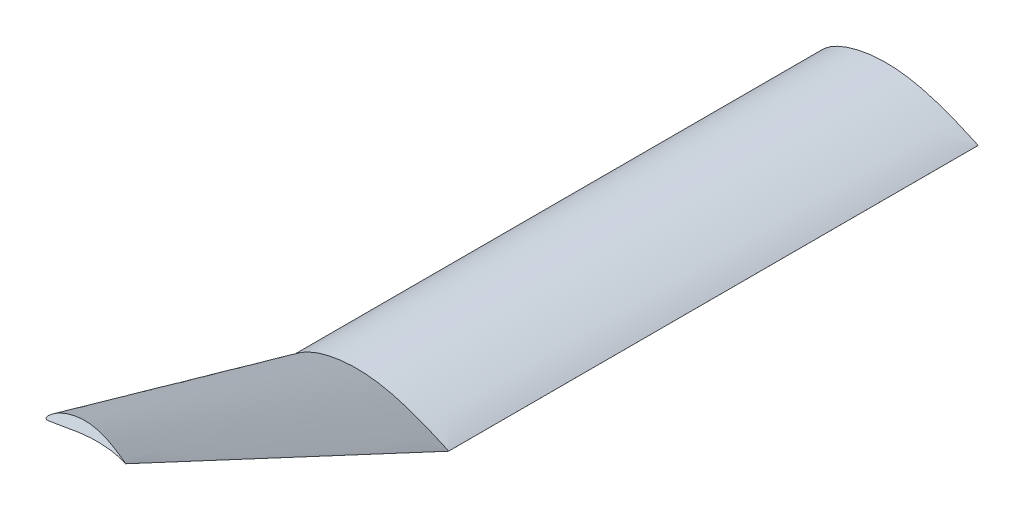
SolidWorks part; units mm, degrees
ref_plane "Front Plane" through (0, 0, 0) normal (0, 0, 1) x (1, 0, 0)
ref_plane "Top Plane" through (0, 0, 0) normal (0, 1, 0) x (1, 0, 0)
ref_plane "Right Plane" through (0, 0, 0) normal (1, 0, 0) x (0, 0, -1)
curve "Curve1"
curve "Curve6"
curve "Curve7"
curve "Curve8"
sketch "Sketch3" plane through (0, 0, 0) normal (0, 0, 1) x (1, 0, 0)
  line L0 (0, 0) -> (50, 0) construction
  line L1 (0.2298, 0.0405) -> (0.2298, 0.0158) construction
  line L2 (0.1804, 0.0405) -> (0.2298, 0.0405)
  line L3 (0.1804, 0.0405) -> (0.1804, -0.0089)
  line L4 (0.1804, -0.0089) -> (0.2298, -0.0089)
  line L5 (0.2298, 0.0405) -> (0.2298, -0.0089)
  line L6 (0.4642, 0.0242) -> (0.4889, 0.0242)
  line L7 (0.4642, 0.0242) -> (0.4642, -0.0005)
  line L8 (0.4642, -0.0005) -> (0.4889, -0.0005)
  line L9 (0.4889, 0.0242) -> (0.4889, -0.0005)
  line L10 (0.2298, 0.0158) -> (0.2146, 0.0158) construction
  line L11 (0.2146, 0.0158) -> (0.2146, 0.0405) construction
  line L12 (0.2146, 0.0405) -> (0.2298, 0.0405) construction
  line L13 (0, 0) -> (500, 0) construction
  line L14 (0.1804, 0.0458) -> (0.1804, -0.0178) construction
  line L15 (0, 0) -> (0, -165.9812) construction
  line L16 (0, -165.9812) -> (300, -165.9812) construction
  line L17 (72.7802, 36.2202) -> (92.7802, 36.2202) construction
  line L18 (70.2802, 13.7202) -> (95.2802, 13.7202)
  line L19 (70.2802, 13.7202) -> (70.2802, 38.7202)
  line L20 (70.2802, 38.7202) -> (95.2802, 38.7202)
  line L21 (95.2802, 13.7202) -> (95.2802, 38.7202)
  line L22 (92.7802, 16.2202) -> (92.7802, 36.2202) construction
  line L23 (72.7802, 16.2202) -> (92.7802, 16.2202) construction
  line L24 (72.7802, 16.2202) -> (72.7802, 36.2202) construction
  line L25 (300, -0.018) -> (300, 0.015)
  line L26 (172.9506, 31.8748) -> (182.9506, 31.8748)
  line L27 (172.9506, 31.8748) -> (172.9506, 21.8748)
  line L28 (172.9506, 21.8748) -> (182.9506, 21.8748)
  line L29 (182.9506, 31.8748) -> (182.9506, 21.8748)
  spline S0 degree 3 poles (1.0002, -0.0023) (1, 0) (1.0002, 0.0023) (0.9919, 0.0001) (0.9849, 0.0027) (0.9729, 0.003) (0.9609, 0.0043) (0.9483, 0.0054) (0.9357, 0.0065) (0.9231, 0.0077) (0.9104, 0.0088) (0.8978, 0.01) (0.8852, 0.0111) (0.8725, 0.0123) (0.8599, 0.0134) (0.8473, 0.0146) (0.8347, 0.0157) (0.8221, 0.0168) (0.8094, 0.0179) (0.7968, 0.019) (0.7842, 0.0201) (0.7716, 0.0211) (0.759, 0.0222) (0.7464, 0.0232) (0.7337, 0.0243) (0.7211, 0.0253) (0.7085, 0.0263) (0.6959, 0.0273) (0.6833, 0.0283) (0.6706, 0.0293) (0.658, 0.0303) (0.6454, 0.0313) (0.6328, 0.0322) (0.6202, 0.0331) (0.6076, 0.0341) (0.595, 0.035) (0.5823, 0.0358) (0.5697, 0.0367) (0.5571, 0.0375) (0.5446, 0.0384) (0.532, 0.0392) (0.5194, 0.0399) (0.5068, 0.0407) (0.4942, 0.0414) (0.4816, 0.0421) (0.469, 0.0427) (0.4565, 0.0434) (0.4439, 0.044) (0.4313, 0.0445) (0.4188, 0.0451) (0.4062, 0.0456) (0.3936, 0.046) (0.3811, 0.0464) (0.3685, 0.0468) (0.356, 0.0472) (0.3435, 0.0475) (0.3309, 0.0477) (0.3184, 0.0479) (0.3059, 0.0481) (0.2934, 0.0482) (0.2809, 0.0482) (0.2685, 0.0482) (0.256, 0.0481) (0.2436, 0.0479) (0.2312, 0.0477) (0.2189, 0.0474) (0.2065, 0.047) (0.1942, 0.0465) (0.182, 0.0459) (0.1698, 0.0452) (0.1576, 0.0444) (0.1456, 0.0434) (0.1336, 0.0423) (0.1217, 0.0411) (0.1099, 0.0397) (0.0983, 0.038) (0.0868, 0.0362) (0.0756, 0.0342) (0.0647, 0.0319) (0.0541, 0.0294) (0.0441, 0.0266) (0.0348, 0.0236) (0.0266, 0.0205) (0.0197, 0.0175) (0.0142, 0.0146) (0.0101, 0.012) (0.007, 0.0098) (0.0047, 0.0078) (0.003, 0.006) (0.0018, 0.0045) (0.0009, 0.003) (0.0003, 0.0017) (0, 0.0004) (0, -0.0008) (0.0005, -0.0021) (0.0015, -0.0032) (0.0028, -0.0043) (0.0046, -0.0054) (0.0068, -0.0066) (0.0097, -0.0078) (0.0135, -0.0091) (0.0186, -0.0106) (0.0252, -0.0121) (0.0334, -0.0135) (0.043, -0.0148) (0.0536, -0.0159) (0.0648, -0.0167) (0.0764, -0.0173) (0.0882, -0.0177) (0.1003, -0.018) (0.1125, -0.0182) (0.1247, -0.0183) (0.1371, -0.0183) (0.1495, -0.0182) (0.162, -0.0181) (0.1745, -0.0179) (0.187, -0.0176) (0.1996, -0.0174) (0.2122, -0.0171) (0.2248, -0.0167) (0.2375, -0.0164) (0.2501, -0.016) (0.2628, -0.0156) (0.2755, -0.0152) (0.2882, -0.0147) (0.3009, -0.0143) (0.3136, -0.0139) (0.3263, -0.0134) (0.339, -0.0129) (0.3517, -0.0125) (0.3644, -0.012) (0.3771, -0.0116) (0.3897, -0.0111) (0.4024, -0.0106) (0.4151, -0.0102) (0.4277, -0.0098) (0.4404, -0.0093) (0.4531, -0.0089) (0.4657, -0.0085) (0.4784, -0.0081) (0.4911, -0.0077) (0.5037, -0.0073) (0.5164, -0.0069) (0.5291, -0.0066) (0.5417, -0.0062) (0.5544, -0.0059) (0.5671, -0.0055) (0.5798, -0.0052) (0.5924, -0.0049) (0.6051, -0.0046) (0.6178, -0.0044) (0.6304, -0.0041) (0.6431, -0.0039) (0.6558, -0.0036) (0.6685, -0.0034) (0.6811, -0.0032) (0.6938, -0.003) (0.7065, -0.0029) (0.7192, -0.0027) (0.7318, -0.0026) (0.7445, -0.0024) (0.7572, -0.0023) (0.7699, -0.0022) (0.7826, -0.0021) (0.7953, -0.002) (0.8079, -0.0019) (0.8206, -0.0019) (0.8333, -0.0018) (0.846, -0.0017) (0.8588, -0.0017) (0.8715, -0.0016) (0.8842, -0.0015) (0.8969, -0.0015) (0.9096, -0.0014) (0.9223, -0.0013) (0.935, -0.0012) (0.9477, -0.0011) (0.9604, -0.0011) (0.9725, -0.0007) (0.9848, -0.0014) (0.9918, 0.0007) (1.0002, -0.0023) (1, 0) (1.0002, 0.0023) knots -0.007874 -0.002894 -0.000332 0 0.000332 0.002885 0.007815 0.013623 0.01978 0.026037 0.032316 0.038604 0.044895 0.051184 0.057469 0.06375 0.070028 0.076304 0.082578 0.088851 0.095124 0.101396 0.107668 0.113941 0.120213 0.126487 0.132762 0.139036 0.145311 0.151585 0.157859 0.16413 0.170401 0.17667 0.182937 0.189202 0.195466 0.201728 0.207987 0.214245 0.2205 0.226754 0.233005 0.239253 0.2455 0.251744 0.257986 0.264226 0.270464 0.2767 0.282933 0.289165 0.295394 0.30162 0.307843 0.314063 0.32028 0.326491 0.332699 0.3389 0.345096 0.351285 0.357467 0.363641 0.369805 0.375959 0.382101 0.38823 0.394345 0.400443 0.406521 0.412577 0.418607 0.424607 0.430573 0.436498 0.442374 0.448192 0.453938 0.459595 0.465142 0.470542 0.475738 0.480625 0.48504 0.488808 0.491844 0.494208 0.496047 0.497501 0.498679 0.499657 0.500486 0.501199 0.501823 0.502412 0.503041 0.50376 0.504602 0.505602 0.50682 0.508337 0.510284 0.512841 0.516185 0.520365 0.525232 0.530552 0.536146 0.541914 0.547804 0.553781 0.559821 0.565909 0.57203 0.578179 0.584352 0.590546 0.596759 0.60299 0.609237 0.615497 0.621768 0.62805 0.634339 0.640634 0.646932 0.653231 0.659529 0.665824 0.672115 0.678404 0.684692 0.690977 0.69726 0.703542 0.709822 0.716099 0.722375 0.728651 0.734927 0.741206 0.747487 0.753768 0.76005 0.766331 0.772611 0.778892 0.785172 0.791451 0.79773 0.804009 0.810289 0.816569 0.822848 0.829126 0.835406 0.841685 0.847965 0.854245 0.860527 0.866808 0.87309 0.879373 0.885657 0.891942 0.898228 0.904515 0.910804 0.917095 0.923389 0.929686 0.935986 0.942288 0.948588 0.954885 0.961183 0.96748 0.973774 0.980051 0.986247 0.992126 0.997106 0.999668 1 1.000332 1.002885 1.007815 only from (1, 0) to (1, 0) construction
  spline S1 degree 3 poles (1.0002, -0.0023) (1, 0) (1.0002, 0.0023) (0.9919, 0.0001) (0.9849, 0.0027) (0.9729, 0.003) (0.9609, 0.0043) (0.9483, 0.0054) (0.9357, 0.0065) (0.9231, 0.0077) (0.9104, 0.0088) (0.8978, 0.01) (0.8852, 0.0111) (0.8725, 0.0123) (0.8599, 0.0134) (0.8473, 0.0146) (0.8347, 0.0157) (0.8221, 0.0168) (0.8094, 0.0179) (0.7968, 0.019) (0.7842, 0.0201) (0.7716, 0.0211) (0.759, 0.0222) (0.7464, 0.0232) (0.7337, 0.0243) (0.7211, 0.0253) (0.7085, 0.0263) (0.6959, 0.0273) (0.6833, 0.0283) (0.6706, 0.0293) (0.658, 0.0303) (0.6454, 0.0313) (0.6328, 0.0322) (0.6202, 0.0331) (0.6076, 0.0341) (0.595, 0.035) (0.5823, 0.0358) (0.5697, 0.0367) (0.5571, 0.0375) (0.5446, 0.0384) (0.532, 0.0392) (0.5194, 0.0399) (0.5068, 0.0407) (0.4942, 0.0414) (0.4816, 0.0421) (0.469, 0.0427) (0.4565, 0.0434) (0.4439, 0.044) (0.4313, 0.0445) (0.4188, 0.0451) (0.4062, 0.0456) (0.3936, 0.046) (0.3811, 0.0464) (0.3685, 0.0468) (0.356, 0.0472) (0.3435, 0.0475) (0.3309, 0.0477) (0.3184, 0.0479) (0.3059, 0.0481) (0.2934, 0.0482) (0.2809, 0.0482) (0.2685, 0.0482) (0.256, 0.0481) (0.2436, 0.0479) (0.2312, 0.0477) (0.2189, 0.0474) (0.2065, 0.047) (0.1942, 0.0465) (0.182, 0.0459) (0.1698, 0.0452) (0.1576, 0.0444) (0.1456, 0.0434) (0.1336, 0.0423) (0.1217, 0.0411) (0.1099, 0.0397) (0.0983, 0.038) (0.0868, 0.0362) (0.0756, 0.0342) (0.0647, 0.0319) (0.0541, 0.0294) (0.0441, 0.0266) (0.0348, 0.0236) (0.0266, 0.0205) (0.0197, 0.0175) (0.0142, 0.0146) (0.0101, 0.012) (0.007, 0.0098) (0.0047, 0.0078) (0.003, 0.006) (0.0018, 0.0045) (0.0009, 0.003) (0.0003, 0.0017) (0, 0.0004) (0, -0.0008) (0.0005, -0.0021) (0.0015, -0.0032) (0.0028, -0.0043) (0.0046, -0.0054) (0.0068, -0.0066) (0.0097, -0.0078) (0.0135, -0.0091) (0.0186, -0.0106) (0.0252, -0.0121) (0.0334, -0.0135) (0.043, -0.0148) (0.0536, -0.0159) (0.0648, -0.0167) (0.0764, -0.0173) (0.0882, -0.0177) (0.1003, -0.018) (0.1125, -0.0182) (0.1247, -0.0183) (0.1371, -0.0183) (0.1495, -0.0182) (0.162, -0.0181) (0.1745, -0.0179) (0.187, -0.0176) (0.1996, -0.0174) (0.2122, -0.0171) (0.2248, -0.0167) (0.2375, -0.0164) (0.2501, -0.016) (0.2628, -0.0156) (0.2755, -0.0152) (0.2882, -0.0147) (0.3009, -0.0143) (0.3136, -0.0139) (0.3263, -0.0134) (0.339, -0.0129) (0.3517, -0.0125) (0.3644, -0.012) (0.3771, -0.0116) (0.3897, -0.0111) (0.4024, -0.0106) (0.4151, -0.0102) (0.4277, -0.0098) (0.4404, -0.0093) (0.4531, -0.0089) (0.4657, -0.0085) (0.4784, -0.0081) (0.4911, -0.0077) (0.5037, -0.0073) (0.5164, -0.0069) (0.5291, -0.0066) (0.5417, -0.0062) (0.5544, -0.0059) (0.5671, -0.0055) (0.5798, -0.0052) (0.5924, -0.0049) (0.6051, -0.0046) (0.6178, -0.0044) (0.6304, -0.0041) (0.6431, -0.0039) (0.6558, -0.0036) (0.6685, -0.0034) (0.6811, -0.0032) (0.6938, -0.003) (0.7065, -0.0029) (0.7192, -0.0027) (0.7318, -0.0026) (0.7445, -0.0024) (0.7572, -0.0023) (0.7699, -0.0022) (0.7826, -0.0021) (0.7953, -0.002) (0.8079, -0.0019) (0.8206, -0.0019) (0.8333, -0.0018) (0.846, -0.0017) (0.8588, -0.0017) (0.8715, -0.0016) (0.8842, -0.0015) (0.8969, -0.0015) (0.9096, -0.0014) (0.9223, -0.0013) (0.935, -0.0012) (0.9477, -0.0011) (0.9604, -0.0011) (0.9725, -0.0007) (0.9848, -0.0014) (0.9918, 0.0007) (1.0002, -0.0023) (1, 0) (1.0002, 0.0023) knots -0.007874 -0.002894 -0.000332 0 0.000332 0.002885 0.007815 0.013623 0.01978 0.026037 0.032316 0.038604 0.044895 0.051184 0.057469 0.06375 0.070028 0.076304 0.082578 0.088851 0.095124 0.101396 0.107668 0.113941 0.120213 0.126487 0.132762 0.139036 0.145311 0.151585 0.157859 0.16413 0.170401 0.17667 0.182937 0.189202 0.195466 0.201728 0.207987 0.214245 0.2205 0.226754 0.233005 0.239253 0.2455 0.251744 0.257986 0.264226 0.270464 0.2767 0.282933 0.289165 0.295394 0.30162 0.307843 0.314063 0.32028 0.326491 0.332699 0.3389 0.345096 0.351285 0.357467 0.363641 0.369805 0.375959 0.382101 0.38823 0.394345 0.400443 0.406521 0.412577 0.418607 0.424607 0.430573 0.436498 0.442374 0.448192 0.453938 0.459595 0.465142 0.470542 0.475738 0.480625 0.48504 0.488808 0.491844 0.494208 0.496047 0.497501 0.498679 0.499657 0.500486 0.501199 0.501823 0.502412 0.503041 0.50376 0.504602 0.505602 0.50682 0.508337 0.510284 0.512841 0.516185 0.520365 0.525232 0.530552 0.536146 0.541914 0.547804 0.553781 0.559821 0.565909 0.57203 0.578179 0.584352 0.590546 0.596759 0.60299 0.609237 0.615497 0.621768 0.62805 0.634339 0.640634 0.646932 0.653231 0.659529 0.665824 0.672115 0.678404 0.684692 0.690977 0.69726 0.703542 0.709822 0.716099 0.722375 0.728651 0.734927 0.741206 0.747487 0.753768 0.76005 0.766331 0.772611 0.778892 0.785172 0.791451 0.79773 0.804009 0.810289 0.816569 0.822848 0.829126 0.835406 0.841685 0.847965 0.854245 0.860527 0.866808 0.87309 0.879373 0.885657 0.891942 0.898228 0.904515 0.910804 0.917095 0.923389 0.929686 0.935986 0.942288 0.948588 0.954885 0.961183 0.96748 0.973774 0.980051 0.986247 0.992126 0.997106 0.999668 1 1.000332 1.002885 1.007815 only from (1, 0) to (1, 0) construction
  spline S2 degree 3 poles (500.0959, -1.1537) (499.9892, 0.0005) (500.0921, 1.1423) (495.9334, 0.0411) (492.471, 1.3334) (486.441, 1.5239) (480.4457, 2.1624) (474.1516, 2.6955) (467.853, 3.2724) (461.5326, 3.8433) (455.2123, 4.419) (448.8921, 4.9943) (442.5755, 5.5699) (436.262, 6.142) (429.9511, 6.7101) (423.6424, 7.2769) (417.3349, 7.8378) (411.0282, 8.3936) (404.7219, 8.9456) (398.4154, 9.4908) (392.1084, 10.0313) (385.8007, 10.567) (379.4922, 11.0968) (373.1826, 11.6221) (366.8717, 12.1412) (360.56, 12.6562) (354.2482, 13.167) (347.9364, 13.6717) (341.6252, 14.172) (335.3149, 14.6658) (329.0056, 15.1544) (322.6972, 15.6341) (316.3902, 16.1098) (310.0841, 16.5743) (303.7793, 17.0336) (297.4758, 17.4828) (291.1738, 17.9236) (284.8734, 18.3542) (278.5742, 18.7741) (272.2766, 19.1842) (265.9803, 19.5806) (259.6857, 19.9669) (253.3925, 20.3385) (247.1009, 20.6976) (240.8108, 21.0438) (234.5219, 21.3728) (228.2344, 21.6877) (221.9482, 21.986) (215.6634, 22.269) (209.38, 22.5336) (203.0985, 22.7823) (196.8192, 23.011) (190.5422, 23.2214) (184.2678, 23.4112) (177.9968, 23.5814) (171.7294, 23.7279) (165.4666, 23.8538) (159.2085, 23.9536) (152.9563, 24.0285) (146.7104, 24.0763) (140.4718, 24.0951) (134.2418, 24.0833) (128.0212, 24.0398) (121.8114, 23.9589) (115.6139, 23.8431) (109.4305, 23.6857) (103.2636, 23.4864) (97.1155, 23.2386) (90.9895, 22.9417) (84.8889, 22.5902) (78.8182, 22.1795) (72.7826, 21.7035) (66.7884, 21.1583) (60.844, 20.5334) (54.9591, 19.8268) (49.1468, 19.0246) (43.424, 18.1218) (37.8124, 17.1067) (32.343, 15.9694) (27.0604, 14.7062) (22.0393, 13.3164) (17.395, 11.8221) (13.2795, 10.2688) (9.8299, 8.731) (7.0994, 7.2913) (5.0301, 6.0034) (3.4945, 4.8762) (2.3559, 3.8907) (1.5099, 3.0166) (0.8848, 2.2285) (0.4335, 1.5087) (0.1314, 0.8425) (-0.0182, 0.2062) (0.0104, -0.4232) (0.2632, -1.0376) (0.7397, -1.6094) (1.4111, -2.154) (2.2826, -2.7045) (3.4007, -3.2811) (4.8511, -3.898) (6.7651, -4.5654) (9.3055, -5.2886) (12.6143, -6.039) (16.7206, -6.7632) (21.5126, -7.4019) (26.7966, -7.9252) (32.394, -8.3361) (38.1897, -8.6462) (44.118, -8.8675) (50.1404, -9.0195) (56.2306, -9.1096) (62.3698, -9.1496) (68.5456, -9.1443) (74.75, -9.104) (80.9785, -9.0332) (87.2282, -8.9364) (93.4969, -8.818) (99.783, -8.6804) (106.0845, -8.5272) (112.3995, -8.3597) (118.7258, -8.1811) (125.0618, -7.9892) (131.4053, -7.7924) (137.7541, -7.5838) (144.1059, -7.37) (150.4584, -7.1501) (156.8097, -6.9267) (163.1584, -6.6992) (169.5042, -6.4709) (175.8475, -6.2404) (182.1887, -6.0105) (188.5278, -5.7806) (194.865, -5.5531) (201.2002, -5.325) (207.5338, -5.1031) (213.8656, -4.8806) (220.1961, -4.6635) (226.5264, -4.4495) (232.8578, -4.2412) (239.1911, -4.0373) (245.5262, -3.8375) (251.8626, -3.6436) (258.1993, -3.458) (264.5356, -3.2755) (270.8718, -3.1019) (277.2076, -2.9318) (283.5434, -2.7691) (289.8787, -2.6119) (296.2141, -2.4645) (302.5496, -2.3201) (308.8856, -2.184) (315.2216, -2.0569) (321.5574, -1.9335) (327.8933, -1.8191) (334.2294, -1.7131) (340.5661, -1.6125) (346.9033, -1.5208) (353.2413, -1.4364) (359.58, -1.3587) (365.9191, -1.2888) (372.2588, -1.223) (378.5993, -1.1661) (384.9408, -1.1114) (391.2835, -1.0632) (397.6273, -1.0167) (403.9727, -0.9749) (410.3197, -0.9366) (416.669, -0.8947) (423.021, -0.8606) (429.376, -0.8257) (435.7337, -0.7924) (442.0922, -0.7597) (448.4498, -0.726) (454.8061, -0.6894) (461.1609, -0.6473) (467.5175, -0.6036) (473.8564, -0.5446) (480.2008, -0.5303) (486.2618, -0.3697) (492.3763, -0.6848) (495.8827, 0.3278) (500.0959, -1.1537) (499.9892, 0.0005) (500.0921, 1.1423) knots -0.007874 -0.002894 -0.000332 0 0.000332 0.002885 0.007815 0.013623 0.01978 0.026037 0.032316 0.038604 0.044895 0.051184 0.057469 0.06375 0.070028 0.076304 0.082578 0.088851 0.095124 0.101396 0.107668 0.113941 0.120213 0.126487 0.132762 0.139036 0.145311 0.151585 0.157859 0.16413 0.170401 0.17667 0.182937 0.189202 0.195466 0.201728 0.207987 0.214245 0.2205 0.226754 0.233005 0.239253 0.2455 0.251744 0.257986 0.264226 0.270464 0.2767 0.282933 0.289165 0.295394 0.30162 0.307843 0.314063 0.32028 0.326491 0.332699 0.3389 0.345096 0.351285 0.357467 0.363641 0.369805 0.375959 0.382101 0.38823 0.394345 0.400443 0.406521 0.412577 0.418607 0.424607 0.430573 0.436498 0.442374 0.448192 0.453938 0.459595 0.465142 0.470542 0.475738 0.480625 0.48504 0.488808 0.491844 0.494208 0.496047 0.497501 0.498679 0.499657 0.500486 0.501199 0.501823 0.502412 0.503041 0.50376 0.504602 0.505602 0.50682 0.508337 0.510284 0.512841 0.516185 0.520365 0.525232 0.530552 0.536146 0.541914 0.547804 0.553781 0.559821 0.565909 0.57203 0.578179 0.584352 0.590546 0.596759 0.60299 0.609237 0.615497 0.621768 0.62805 0.634339 0.640634 0.646932 0.653231 0.659529 0.665824 0.672115 0.678404 0.684692 0.690977 0.69726 0.703542 0.709822 0.716099 0.722375 0.728651 0.734927 0.741206 0.747487 0.753768 0.76005 0.766331 0.772611 0.778892 0.785172 0.791451 0.79773 0.804009 0.810289 0.816569 0.822848 0.829126 0.835406 0.841685 0.847965 0.854245 0.860527 0.866808 0.87309 0.879373 0.885657 0.891942 0.898228 0.904515 0.910804 0.917095 0.923389 0.929686 0.935986 0.942288 0.948588 0.954885 0.961183 0.96748 0.973774 0.980051 0.986247 0.992126 0.997106 0.999668 1 1.000332 1.002885 1.007815 only from (500, 0) to (500, 0) construction
  spline S3 degree 3 poles (0.0009, 0.0052) (-0.0004, 0.0004) (0.0009, -0.0041) (0.0046, -0.0077) (0.01, -0.0109) (0.0176, -0.0135) (0.0271, -0.0161) (0.0387, -0.0182) (0.0522, -0.0201) (0.0676, -0.0217) (0.0848, -0.023) (0.1039, -0.024) (0.1246, -0.0248) (0.147, -0.0252) (0.1708, -0.0253) (0.1961, -0.0249) (0.2226, -0.0244) (0.2504, -0.0233) (0.2792, -0.022) (0.3089, -0.0201) (0.3395, -0.018) (0.3708, -0.0154) (0.4026, -0.0128) (0.4348, -0.0098) (0.4673, -0.0069) (0.5, -0.0039) (0.5326, -0.0011) (0.5652, 0.0016) (0.5974, 0.004) (0.6292, 0.0062) (0.6605, 0.0079) (0.6911, 0.0092) (0.7208, 0.0102) (0.7496, 0.0109) (0.7774, 0.0112) (0.8039, 0.0112) (0.8292, 0.0108) (0.8531, 0.0102) (0.8754, 0.0093) (0.8961, 0.0083) (0.9151, 0.0072) (0.9324, 0.006) (0.9478, 0.0048) (0.9613, 0.0036) (0.9728, 0.0025) (0.9823, 0.0014) (0.9896, 0.0009) (0.9953, 0) (0.9977, 0.0003) (1.0006, -0.0001) (0.9978, 0.0008) (0.9953, 0.0005) (0.9896, 0.0024) (0.9823, 0.0038) (0.9728, 0.0059) (0.9613, 0.0083) (0.9478, 0.0111) (0.9324, 0.0142) (0.9151, 0.0177) (0.8961, 0.0215) (0.8754, 0.0255) (0.8531, 0.0298) (0.8292, 0.0342) (0.804, 0.0388) (0.7774, 0.0435) (0.7497, 0.0482) (0.7209, 0.0527) (0.6911, 0.057) (0.6605, 0.0611) (0.6292, 0.0649) (0.5974, 0.0683) (0.5652, 0.0714) (0.5327, 0.074) (0.5, 0.0763) (0.4674, 0.0782) (0.4348, 0.0796) (0.4026, 0.0805) (0.3708, 0.0807) (0.3395, 0.0805) (0.3089, 0.0796) (0.2792, 0.0783) (0.2503, 0.0762) (0.2226, 0.0737) (0.196, 0.0706) (0.1707, 0.0671) (0.1469, 0.063) (0.1245, 0.0586) (0.1038, 0.0538) (0.0847, 0.0488) (0.0675, 0.0434) (0.052, 0.0379) (0.0385, 0.0321) (0.027, 0.0264) (0.0174, 0.0207) (0.01, 0.0151) (0.0045, 0.01) (0.0009, 0.0052) (-0.0004, 0.0004) (0.0009, -0.0041) knots -0.00884 -0.005198 -0.002428 0 0.00188 0.004212 0.007287 0.011193 0.016028 0.021799 0.028506 0.036135 0.044658 0.05404 0.064256 0.075258 0.087001 0.099438 0.112517 0.126192 0.1404 0.155081 0.170175 0.18562 0.201344 0.217287 0.233363 0.249508 0.265648 0.281715 0.297638 0.313339 0.328759 0.343831 0.358493 0.372688 0.386355 0.39943 0.411868 0.423614 0.434623 0.444843 0.454228 0.462746 0.470357 0.477022 0.482719 0.487411 0.491081 0.493714 0.495293 0.495821 0.496379 0.497969 0.500662 0.504411 0.509181 0.514974 0.521753 0.529496 0.538165 0.547715 0.558116 0.569314 0.581261 0.593902 0.607179 0.621035 0.635401 0.650209 0.6654 0.680908 0.696666 0.712615 0.72868 0.744799 0.760906 0.776932 0.792816 0.808483 0.82388 0.838944 0.853614 0.86784 0.881563 0.894727 0.907286 0.919199 0.930414 0.940893 0.950586 0.959485 0.967557 0.974773 0.981115 0.986579 0.99116 0.994802 0.997572 1 1.00188 1.004212 1.007287 only from (0, 0) to (0, 0) construction
  spline S4 degree 3 poles (0.0009, 0.0052) (-0.0004, 0.0004) (0.0009, -0.0041) (0.0046, -0.0077) (0.01, -0.0109) (0.0176, -0.0135) (0.0271, -0.0161) (0.0387, -0.0182) (0.0522, -0.0201) (0.0676, -0.0217) (0.0848, -0.023) (0.1039, -0.024) (0.1246, -0.0248) (0.147, -0.0252) (0.1708, -0.0253) (0.1961, -0.0249) (0.2226, -0.0244) (0.2504, -0.0233) (0.2792, -0.022) (0.3089, -0.0201) (0.3395, -0.018) (0.3708, -0.0154) (0.4026, -0.0128) (0.4348, -0.0098) (0.4673, -0.0069) (0.5, -0.0039) (0.5326, -0.0011) (0.5652, 0.0016) (0.5974, 0.004) (0.6292, 0.0062) (0.6605, 0.0079) (0.6911, 0.0092) (0.7208, 0.0102) (0.7496, 0.0109) (0.7774, 0.0112) (0.8039, 0.0112) (0.8292, 0.0108) (0.8531, 0.0102) (0.8754, 0.0093) (0.8961, 0.0083) (0.9151, 0.0072) (0.9324, 0.006) (0.9478, 0.0048) (0.9613, 0.0036) (0.9728, 0.0025) (0.9823, 0.0014) (0.9896, 0.0009) (0.9953, 0) (0.9977, 0.0003) (1.0006, -0.0001) (0.9978, 0.0008) (0.9953, 0.0005) (0.9896, 0.0024) (0.9823, 0.0038) (0.9728, 0.0059) (0.9613, 0.0083) (0.9478, 0.0111) (0.9324, 0.0142) (0.9151, 0.0177) (0.8961, 0.0215) (0.8754, 0.0255) (0.8531, 0.0298) (0.8292, 0.0342) (0.804, 0.0388) (0.7774, 0.0435) (0.7497, 0.0482) (0.7209, 0.0527) (0.6911, 0.057) (0.6605, 0.0611) (0.6292, 0.0649) (0.5974, 0.0683) (0.5652, 0.0714) (0.5327, 0.074) (0.5, 0.0763) (0.4674, 0.0782) (0.4348, 0.0796) (0.4026, 0.0805) (0.3708, 0.0807) (0.3395, 0.0805) (0.3089, 0.0796) (0.2792, 0.0783) (0.2503, 0.0762) (0.2226, 0.0737) (0.196, 0.0706) (0.1707, 0.0671) (0.1469, 0.063) (0.1245, 0.0586) (0.1038, 0.0538) (0.0847, 0.0488) (0.0675, 0.0434) (0.052, 0.0379) (0.0385, 0.0321) (0.027, 0.0264) (0.0174, 0.0207) (0.01, 0.0151) (0.0045, 0.01) (0.0009, 0.0052) (-0.0004, 0.0004) (0.0009, -0.0041) knots -0.00884 -0.005198 -0.002428 0 0.00188 0.004212 0.007287 0.011193 0.016028 0.021799 0.028506 0.036135 0.044658 0.05404 0.064256 0.075258 0.087001 0.099438 0.112517 0.126192 0.1404 0.155081 0.170175 0.18562 0.201344 0.217287 0.233363 0.249508 0.265648 0.281715 0.297638 0.313339 0.328759 0.343831 0.358493 0.372688 0.386355 0.39943 0.411868 0.423614 0.434623 0.444843 0.454228 0.462746 0.470357 0.477022 0.482719 0.487411 0.491081 0.493714 0.495293 0.495821 0.496379 0.497969 0.500662 0.504411 0.509181 0.514974 0.521753 0.529496 0.538165 0.547715 0.558116 0.569314 0.581261 0.593902 0.607179 0.621035 0.635401 0.650209 0.6654 0.680908 0.696666 0.712615 0.72868 0.744799 0.760906 0.776932 0.792816 0.808483 0.82388 0.838944 0.853614 0.86784 0.881563 0.894727 0.907286 0.919199 0.930414 0.940893 0.950586 0.959485 0.967557 0.974773 0.981115 0.986579 0.99116 0.994802 0.997572 1 1.00188 1.004212 1.007287 only from (0, 0) to (0, 0)
  spline S6 degree 3 poles (1643.0294, 2510.6121) (-0.9132, -4.9999) (1.4845, -0.2863) (0.9897, 0.0065) (0.9795, 0.0117) (0.966, 0.0177) (0.9494, 0.025) (0.9297, 0.0336) (0.8975, 0.0473) (0.8617, 0.0622) (0.8225, 0.0776) (0.79, 0.0897) (0.7558, 0.1017) (0.7079, 0.1172) (0.6584, 0.1311) (0.6078, 0.1427) (0.5695, 0.1499) (0.5311, 0.1556) (0.4927, 0.1597) (0.4545, 0.162) (0.4165, 0.1627) (0.3791, 0.1616) (0.3305, 0.1581) (0.2833, 0.1514) (0.2379, 0.1418) (0.2058, 0.1335) (0.1754, 0.124) (0.1469, 0.1134) (0.1204, 0.1018) (0.0962, 0.0895) (0.0744, 0.0767) (0.0552, 0.0638) (0.0386, 0.051) (0.0247, 0.0387) (0.0137, 0.027) (0.0057, 0.0163) (0.0011, 0.0075) (-0.0003, 0.0005) (0.0007, -0.0053) (0.0058, -0.01) (0.0142, -0.0123) (0.0253, -0.0129) (0.0391, -0.0122) (0.0556, -0.0102) (0.0748, -0.0075) (0.0966, -0.0042) (0.1207, -0.0007) (0.1472, 0.0033) (0.1757, 0.0076) (0.2172, 0.0138) (0.2609, 0.02) (0.3311, 0.0293) (0.3922, 0.0363) (0.4672, 0.043) (0.531, 0.0474) (0.5949, 0.0495) (0.6458, 0.0495) (0.6833, 0.0486) (0.7201, 0.0469) (0.7557, 0.0444) (0.7899, 0.0412) (0.8225, 0.0376) (0.853, 0.0334) (0.8812, 0.0289) (0.9069, 0.0241) (0.9297, 0.0193) (0.9494, 0.0145) (0.966, 0.0098) (0.9793, 0.0054) (0.9895, 0.0024) (1.5167, -0.1309) (3.0282, 4.3648) (-623.5231, -2934.0731) knots -0.813001 -0.813001 -0.813001 -0.813001 0.001413 0.005226 0.010781 0.017816 0.026461 0.036791 0.048686 0.076639 0.092363 0.109003 0.126387 0.144339 0.181313 0.200023 0.218713 0.237261 0.255692 0.274037 0.292193 0.310133 0.327788 0.362002 0.378421 0.394287 0.409543 0.424114 0.437938 0.450942 0.463044 0.474154 0.484165 0.493024 0.500713 0.507126 0.51213 0.514904 0.517171 0.520262 0.524245 0.529498 0.536092 0.544061 0.553363 0.563905 0.575615 0.58842 0.602227 0.616944 0.648676 0.665501 0.718564 0.736789 0.773513 0.810245 0.828489 0.846493 0.864125 0.881249 0.897725 0.913415 0.928184 0.941897 0.954411 0.965603 0.97535 0.983576 0.990285 0.995433 0.9988 1.769799 1.769799 1.769799 1.769799 only from (1, 0.0001) to (1, -0.0001) construction
  spline S7 degree 3 poles (1, 0.0001) (0.9992, 0.0006) (0.9962, 0.0026) (0.9897, 0.0065) (0.9795, 0.0117) (0.966, 0.0177) (0.9494, 0.025) (0.9297, 0.0336) (0.8975, 0.0473) (0.8617, 0.0622) (0.8225, 0.0776) (0.79, 0.0897) (0.7558, 0.1017) (0.7079, 0.1172) (0.6584, 0.1311) (0.6078, 0.1427) (0.5695, 0.1499) (0.5311, 0.1556) (0.4927, 0.1597) (0.4545, 0.162) (0.4165, 0.1627) (0.3791, 0.1616) (0.3305, 0.1581) (0.2833, 0.1514) (0.2379, 0.1418) (0.2058, 0.1335) (0.1754, 0.124) (0.1469, 0.1134) (0.1204, 0.1018) (0.0962, 0.0895) (0.0744, 0.0767) (0.0552, 0.0638) (0.0386, 0.051) (0.0247, 0.0387) (0.0137, 0.027) (0.0057, 0.0163) (0.0011, 0.0075) (-0.0003, 0.0005) (0.0007, -0.0053) (0.0058, -0.01) (0.0142, -0.0123) (0.0253, -0.0129) (0.0391, -0.0122) (0.0556, -0.0102) (0.0748, -0.0075) (0.0966, -0.0042) (0.1207, -0.0007) (0.1472, 0.0033) (0.1757, 0.0076) (0.2172, 0.0138) (0.2609, 0.02) (0.3311, 0.0293) (0.3922, 0.0363) (0.4672, 0.043) (0.531, 0.0474) (0.5949, 0.0495) (0.6458, 0.0495) (0.6833, 0.0486) (0.7201, 0.0469) (0.7557, 0.0444) (0.7899, 0.0412) (0.8225, 0.0376) (0.853, 0.0334) (0.8812, 0.0289) (0.9069, 0.0241) (0.9297, 0.0193) (0.9494, 0.0145) (0.966, 0.0098) (0.9793, 0.0054) (0.9895, 0.0024) (0.9961, 0.0007) (0.9992, 0.0001) (1, -0.0001) knots 0 0 0 0 0.001413 0.005226 0.010781 0.017816 0.026461 0.036791 0.048686 0.076639 0.092363 0.109003 0.126387 0.144339 0.181313 0.200023 0.218713 0.237261 0.255692 0.274037 0.292193 0.310133 0.327788 0.362002 0.378421 0.394287 0.409543 0.424114 0.437938 0.450942 0.463044 0.474154 0.484165 0.493024 0.500713 0.507126 0.51213 0.514904 0.517171 0.520262 0.524245 0.529498 0.536092 0.544061 0.553363 0.563905 0.575615 0.58842 0.602227 0.616944 0.648676 0.665501 0.718564 0.736789 0.773513 0.810245 0.828489 0.846493 0.864125 0.881249 0.897725 0.913415 0.928184 0.941897 0.954411 0.965603 0.97535 0.983576 0.990285 0.995433 0.9988 1 1 1 1
  spline S8 degree 3 poles (300, 0.015) (299.7549, 0.1803) (298.8485, 0.7916) (296.9058, 1.9408) (293.8466, 3.4981) (289.7862, 5.3006) (284.8109, 7.501) (278.8968, 10.0932) (269.2354, 14.1942) (258.4984, 18.6488) (246.7587, 23.2716) (237.0102, 26.9128) (226.7497, 30.5099) (212.3568, 35.1631) (197.5225, 39.3346) (182.3532, 42.7985) (170.8532, 44.983) (159.3316, 46.6908) (147.8202, 47.91) (136.3478, 48.6095) (124.9585, 48.8071) (113.7162, 48.4849) (99.1486, 47.4166) (84.9892, 45.4203) (71.3746, 42.5477) (61.7481, 40.04) (52.6211, 37.1899) (44.0583, 34.0079) (36.1164, 30.545) (28.8549, 26.8491) (22.3219, 23.0051) (16.5503, 19.1272) (11.572, 15.306) (7.4224, 11.6043) (4.1227, 8.1029) (1.7178, 4.9011) (0.3395, 2.2392) (-0.1024, 0.1583) (0.204, -1.5858) (1.7337, -3.0118) (4.2692, -3.6752) (7.5793, -3.8829) (11.7249, -3.6469) (16.6836, -3.0728) (22.4426, -2.246) (28.9693, -1.2656) (36.224, -0.1978) (44.1511, 0.9911) (52.7004, 2.2732) (65.1658, 4.1342) (78.2672, 6.0122) (99.3394, 8.8005) (117.6535, 10.8907) (140.1569, 12.9054) (159.2914, 14.2176) (178.4661, 14.8407) (193.7325, 14.8395) (205.0007, 14.5833) (216.0252, 14.0626) (226.7164, 13.3188) (236.9837, 12.3748) (246.7404, 11.2771) (255.8965, 10.033) (264.365, 8.6788) (272.0599, 7.2435) (278.9039, 5.7843) (284.8344, 4.3498) (289.7985, 2.9258) (293.7954, 1.6329) (296.8452, 0.7155) (298.8166, 0.2169) (299.7538, 0.0309) (300, -0.018) knots 0 0 0 0 0.001413 0.005226 0.010781 0.017816 0.026461 0.036791 0.048686 0.076639 0.092363 0.109003 0.126387 0.144339 0.181313 0.200023 0.218713 0.237261 0.255692 0.274037 0.292193 0.310133 0.327788 0.362002 0.378421 0.394287 0.409543 0.424114 0.437938 0.450942 0.463044 0.474154 0.484165 0.493024 0.500713 0.507126 0.51213 0.514904 0.517171 0.520262 0.524245 0.529498 0.536092 0.544061 0.553363 0.563905 0.575615 0.58842 0.602227 0.616944 0.648676 0.665501 0.718564 0.736789 0.773513 0.810245 0.828489 0.846493 0.864125 0.881249 0.897725 0.913415 0.928184 0.941897 0.954411 0.965603 0.97535 0.983576 0.990285 0.995433 0.9988 1 1 1 1
  dimension "D1" = 300
  dimension "D2" = 25
  dimension "D3" = 2.5
  dimension "D4" = 20
  dimension "D5" = 10
extrude "Boss-Extrude1" add sketch "Sketch3" along normal blind 1000 contours L25 S8 L3 L2 L5 L4 L26 L29 L28 L27 L6 L9 L8 L7 L21 L18 L19 L20 region at (0.2962, 0.0449, 0) region at (0.1705, -0.0003, 0) region at (0.005, -0.0079, 0) region at (125.7868, 23.7644, 0) region at (0.8963, 0.0231, 0) region at (0.4716, 0.099, 0) region at (0.9981, 0.0004, 0)
sketch "Sketch5" plane through (0, 0, 0) normal (1, 0, 0) x (0, 0, -1)
  line L0 (-1000, 26.2202) -> (-1600, 306.0048) construction
  line L1 (-1000, 26.2202) -> (-928.4406, 26.2202) construction
  line L2 (-1000, 26.2202) -> (-1200.048, 26.2202) construction
  line L4 (0, 13.7202) -> (0, 38.7202)
  line L5 (0, 38.7202) -> (-1000, 38.7202)
  line L6 (-1000, 38.7202) -> (-1000, 13.7202)
  line L7 (-1000, 13.7202) -> (0, 13.7202)
  line L10 (-1000, 38.7202) -> (-1000, 13.7202) construction
  dimension "D2" = 25
  dimension "D3" = 600
  dimension "D1" = 0
ref_plane "Plane1" through (0, 306.0048, 1600) normal (0, 0.4226, 0.9063) x (1, 0, 0)
sketch "Sketch6" plane through (0, 306.0048, 1600) normal (0, 0.4226, 0.9063) x (1, 0, 0)
  line L0 (0, -49.6836) -> (50, -49.6836) construction
  line L13 (0, -49.6836) -> (500, -49.6836) construction
  line L14 (300, -23.7665) -> (150, -23.7665) construction
  line L15 (0, -49.6836) -> (0, -146.6712) construction
  line L16 (0, -146.6712) -> (300, -146.6712) construction
  line L25 (300, -23.7665) -> (300, -23.75)
  line L31 (300, -23.7799) -> (300, -23.75)
  line L32 (300, -23.7799) -> (300, -23.75) construction
  spline S0 degree 3 poles (-457.9361, -49.6859) (-457.9364, -49.6836) (-457.9362, -49.6813) (-457.9445, -49.6835) (-457.9514, -49.6809) (-457.9635, -49.6806) (-457.9754, -49.6793) (-457.988, -49.6782) (-458.0006, -49.6771) (-458.0133, -49.6759) (-458.0259, -49.6748) (-458.0386, -49.6736) (-458.0512, -49.6725) (-458.0638, -49.6713) (-458.0764, -49.6702) (-458.0891, -49.6691) (-458.1017, -49.6679) (-458.1143, -49.6668) (-458.1269, -49.6657) (-458.1395, -49.6646) (-458.1521, -49.6635) (-458.1647, -49.6625) (-458.1774, -49.6614) (-458.19, -49.6604) (-458.2026, -49.6593) (-458.2152, -49.6583) (-458.2278, -49.6573) (-458.2405, -49.6563) (-458.2531, -49.6553) (-458.2657, -49.6543) (-458.2783, -49.6533) (-458.2909, -49.6523) (-458.3036, -49.6514) (-458.3162, -49.6505) (-458.3288, -49.6495) (-458.3414, -49.6486) (-458.354, -49.6478) (-458.3666, -49.6469) (-458.3792, -49.6461) (-458.3918, -49.6452) (-458.4044, -49.6444) (-458.417, -49.6437) (-458.4296, -49.6429) (-458.4421, -49.6422) (-458.4547, -49.6415) (-458.4673, -49.6409) (-458.4799, -49.6402) (-458.4924, -49.6396) (-458.505, -49.6391) (-458.5176, -49.6385) (-458.5301, -49.638) (-458.5427, -49.6376) (-458.5553, -49.6372) (-458.5678, -49.6368) (-458.5803, -49.6364) (-458.5929, -49.6361) (-458.6054, -49.6359) (-458.6179, -49.6357) (-458.6304, -49.6355) (-458.6429, -49.6355) (-458.6554, -49.6354) (-458.6679, -49.6354) (-458.6803, -49.6355) (-458.6927, -49.6357) (-458.7051, -49.6359) (-458.7175, -49.6362) (-458.7298, -49.6366) (-458.7421, -49.6371) (-458.7544, -49.6377) (-458.7666, -49.6384) (-458.7787, -49.6392) (-458.7908, -49.6402) (-458.8028, -49.6413) (-458.8147, -49.6425) (-458.8264, -49.644) (-458.838, -49.6456) (-458.8495, -49.6474) (-458.8607, -49.6494) (-458.8717, -49.6517) (-458.8822, -49.6542) (-458.8923, -49.657) (-458.9016, -49.66) (-458.9098, -49.6631) (-458.9167, -49.6661) (-458.9221, -49.669) (-458.9263, -49.6716) (-458.9294, -49.6739) (-458.9316, -49.6758) (-458.9333, -49.6776) (-458.9346, -49.6791) (-458.9355, -49.6806) (-458.9361, -49.6819) (-458.9364, -49.6832) (-458.9363, -49.6845) (-458.9358, -49.6857) (-458.9349, -49.6868) (-458.9335, -49.6879) (-458.9318, -49.689) (-458.9295, -49.6902) (-458.9266, -49.6914) (-458.9228, -49.6927) (-458.9177, -49.6942) (-458.9111, -49.6957) (-458.9029, -49.6971) (-458.8933, -49.6984) (-458.8827, -49.6995) (-458.8716, -49.7003) (-458.86, -49.7009) (-458.8481, -49.7013) (-458.8361, -49.7016) (-458.8239, -49.7018) (-458.8116, -49.7019) (-458.7992, -49.7019) (-458.7868, -49.7018) (-458.7744, -49.7017) (-458.7619, -49.7015) (-458.7493, -49.7012) (-458.7368, -49.701) (-458.7242, -49.7007) (-458.7115, -49.7003) (-458.6989, -49.7) (-458.6862, -49.6996) (-458.6735, -49.6992) (-458.6608, -49.6988) (-458.6481, -49.6983) (-458.6354, -49.6979) (-458.6227, -49.6975) (-458.61, -49.697) (-458.5973, -49.6965) (-458.5846, -49.6961) (-458.572, -49.6956) (-458.5593, -49.6952) (-458.5466, -49.6947) (-458.5339, -49.6943) (-458.5213, -49.6938) (-458.5086, -49.6934) (-458.4959, -49.6929) (-458.4833, -49.6925) (-458.4706, -49.6921) (-458.458, -49.6917) (-458.4453, -49.6913) (-458.4326, -49.6909) (-458.4199, -49.6905) (-458.4073, -49.6902) (-458.3946, -49.6898) (-458.3819, -49.6895) (-458.3693, -49.6891) (-458.3566, -49.6888) (-458.3439, -49.6885) (-458.3312, -49.6882) (-458.3186, -49.688) (-458.3059, -49.6877) (-458.2932, -49.6875) (-458.2806, -49.6872) (-458.2679, -49.687) (-458.2552, -49.6868) (-458.2425, -49.6866) (-458.2299, -49.6865) (-458.2172, -49.6863) (-458.2045, -49.6862) (-458.1918, -49.6861) (-458.1791, -49.6859) (-458.1665, -49.6858) (-458.1538, -49.6857) (-458.1411, -49.6856) (-458.1284, -49.6856) (-458.1157, -49.6855) (-458.103, -49.6854) (-458.0903, -49.6853) (-458.0776, -49.6853) (-458.0649, -49.6852) (-458.0522, -49.6851) (-458.0394, -49.6851) (-458.0267, -49.685) (-458.014, -49.6849) (-458.0013, -49.6848) (-457.9886, -49.6847) (-457.9759, -49.6847) (-457.9638, -49.6843) (-457.9516, -49.685) (-457.9446, -49.6829) (-457.9361, -49.6859) (-457.9364, -49.6836) (-457.9362, -49.6813) knots -0.007874 -0.002894 -0.000332 0 0.000332 0.002885 0.007815 0.013623 0.01978 0.026037 0.032316 0.038604 0.044895 0.051184 0.057469 0.06375 0.070028 0.076304 0.082578 0.088851 0.095124 0.101396 0.107668 0.113941 0.120213 0.126487 0.132762 0.139036 0.145311 0.151585 0.157859 0.16413 0.170401 0.17667 0.182937 0.189202 0.195466 0.201728 0.207987 0.214245 0.2205 0.226754 0.233005 0.239253 0.2455 0.251744 0.257986 0.264226 0.270464 0.2767 0.282933 0.289165 0.295394 0.30162 0.307843 0.314063 0.32028 0.326491 0.332699 0.3389 0.345096 0.351285 0.357467 0.363641 0.369805 0.375959 0.382101 0.38823 0.394345 0.400443 0.406521 0.412577 0.418607 0.424607 0.430573 0.436498 0.442374 0.448192 0.453938 0.459595 0.465142 0.470542 0.475738 0.480625 0.48504 0.488808 0.491844 0.494208 0.496047 0.497501 0.498679 0.499657 0.500486 0.501199 0.501823 0.502412 0.503041 0.50376 0.504602 0.505602 0.50682 0.508337 0.510284 0.512841 0.516185 0.520365 0.525232 0.530552 0.536146 0.541914 0.547804 0.553781 0.559821 0.565909 0.57203 0.578179 0.584352 0.590546 0.596759 0.60299 0.609237 0.615497 0.621768 0.62805 0.634339 0.640634 0.646932 0.653231 0.659529 0.665824 0.672115 0.678404 0.684692 0.690977 0.69726 0.703542 0.709822 0.716099 0.722375 0.728651 0.734927 0.741206 0.747487 0.753768 0.76005 0.766331 0.772611 0.778892 0.785172 0.791451 0.79773 0.804009 0.810289 0.816569 0.822848 0.829126 0.835406 0.841685 0.847965 0.854245 0.860527 0.866808 0.87309 0.879373 0.885657 0.891942 0.898228 0.904515 0.910804 0.917095 0.923389 0.929686 0.935986 0.942288 0.948588 0.954885 0.961183 0.96748 0.973774 0.980051 0.986247 0.992126 0.997106 0.999668 1 1.000332 1.002885 1.007815 only from (-457.9363, -49.6836) to (-457.9363, -49.6836) construction
  spline S1 degree 3 poles (500.0959, -50.8373) (499.9892, -49.6831) (500.0921, -48.5413) (495.9334, -49.6425) (492.471, -48.3502) (486.441, -48.1597) (480.4457, -47.5212) (474.1516, -46.9881) (467.853, -46.4112) (461.5326, -45.8403) (455.2123, -45.2646) (448.8921, -44.6893) (442.5755, -44.1137) (436.262, -43.5416) (429.9511, -42.9735) (423.6424, -42.4067) (417.3349, -41.8458) (411.0282, -41.29) (404.7219, -40.738) (398.4154, -40.1928) (392.1084, -39.6523) (385.8007, -39.1167) (379.4922, -38.5868) (373.1826, -38.0615) (366.8717, -37.5424) (360.56, -37.0274) (354.2482, -36.5166) (347.9364, -36.0119) (341.6252, -35.5116) (335.3149, -35.0178) (329.0056, -34.5292) (322.6972, -34.0495) (316.3902, -33.5738) (310.0841, -33.1093) (303.7793, -32.65) (297.4758, -32.2008) (291.1738, -31.76) (284.8734, -31.3294) (278.5742, -30.9096) (272.2766, -30.4994) (265.9803, -30.103) (259.6857, -29.7167) (253.3925, -29.3451) (247.1009, -28.986) (240.8108, -28.6398) (234.5219, -28.3108) (228.2344, -27.9959) (221.9482, -27.6976) (215.6634, -27.4146) (209.38, -27.15) (203.0985, -26.9013) (196.8192, -26.6726) (190.5422, -26.4622) (184.2678, -26.2724) (177.9968, -26.1022) (171.7294, -25.9557) (165.4666, -25.8298) (159.2085, -25.73) (152.9563, -25.6551) (146.7104, -25.6073) (140.4718, -25.5885) (134.2418, -25.6003) (128.0212, -25.6438) (121.8114, -25.7247) (115.6139, -25.8405) (109.4305, -25.9979) (103.2636, -26.1972) (97.1155, -26.445) (90.9895, -26.7419) (84.8889, -27.0934) (78.8182, -27.5041) (72.7826, -27.9801) (66.7884, -28.5253) (60.844, -29.1502) (54.9591, -29.8568) (49.1468, -30.659) (43.424, -31.5618) (37.8124, -32.5769) (32.343, -33.7142) (27.0604, -34.9774) (22.0393, -36.3672) (17.395, -37.8615) (13.2795, -39.4148) (9.8299, -40.9526) (7.0994, -42.3923) (5.0301, -43.6802) (3.4945, -44.8074) (2.3559, -45.7929) (1.5099, -46.667) (0.8848, -47.4551) (0.4335, -48.1749) (0.1314, -48.8411) (-0.0182, -49.4774) (0.0104, -50.1068) (0.2632, -50.7212) (0.7397, -51.293) (1.4111, -51.8376) (2.2826, -52.3881) (3.4007, -52.9647) (4.8511, -53.5816) (6.7651, -54.249) (9.3055, -54.9722) (12.6143, -55.7226) (16.7206, -56.4468) (21.5126, -57.0855) (26.7966, -57.6088) (32.394, -58.0197) (38.1897, -58.3298) (44.118, -58.5511) (50.1404, -58.7031) (56.2306, -58.7932) (62.3698, -58.8332) (68.5456, -58.8279) (74.75, -58.7876) (80.9785, -58.7168) (87.2282, -58.6201) (93.4969, -58.5016) (99.783, -58.364) (106.0845, -58.2108) (112.3995, -58.0433) (118.7258, -57.8647) (125.0618, -57.6728) (131.4053, -57.476) (137.7541, -57.2674) (144.1059, -57.0536) (150.4584, -56.8337) (156.8097, -56.6104) (163.1584, -56.3828) (169.5042, -56.1545) (175.8475, -55.924) (182.1887, -55.6942) (188.5278, -55.4642) (194.865, -55.2367) (201.2002, -55.0086) (207.5338, -54.7868) (213.8656, -54.5642) (220.1961, -54.3471) (226.5264, -54.1331) (232.8578, -53.9248) (239.1911, -53.7209) (245.5262, -53.5211) (251.8626, -53.3272) (258.1993, -53.1416) (264.5356, -52.9592) (270.8718, -52.7855) (277.2076, -52.6154) (283.5434, -52.4527) (289.8787, -52.2955) (296.2141, -52.1481) (302.5496, -52.0037) (308.8856, -51.8676) (315.2216, -51.7405) (321.5574, -51.6171) (327.8933, -51.5027) (334.2294, -51.3967) (340.5661, -51.2961) (346.9033, -51.2044) (353.2413, -51.12) (359.58, -51.0423) (365.9191, -50.9724) (372.2588, -50.9066) (378.5993, -50.8497) (384.9408, -50.795) (391.2835, -50.7468) (397.6273, -50.7003) (403.9727, -50.6585) (410.3197, -50.6202) (416.669, -50.5783) (423.021, -50.5442) (429.376, -50.5093) (435.7337, -50.476) (442.0922, -50.4433) (448.4498, -50.4096) (454.8061, -50.373) (461.1609, -50.3309) (467.5175, -50.2872) (473.8564, -50.2282) (480.2008, -50.2139) (486.2618, -50.0533) (492.3763, -50.3684) (495.8827, -49.3558) (500.0959, -50.8373) (499.9892, -49.6831) (500.0921, -48.5413) knots -0.007874 -0.002894 -0.000332 0 0.000332 0.002885 0.007815 0.013623 0.01978 0.026037 0.032316 0.038604 0.044895 0.051184 0.057469 0.06375 0.070028 0.076304 0.082578 0.088851 0.095124 0.101396 0.107668 0.113941 0.120213 0.126487 0.132762 0.139036 0.145311 0.151585 0.157859 0.16413 0.170401 0.17667 0.182937 0.189202 0.195466 0.201728 0.207987 0.214245 0.2205 0.226754 0.233005 0.239253 0.2455 0.251744 0.257986 0.264226 0.270464 0.2767 0.282933 0.289165 0.295394 0.30162 0.307843 0.314063 0.32028 0.326491 0.332699 0.3389 0.345096 0.351285 0.357467 0.363641 0.369805 0.375959 0.382101 0.38823 0.394345 0.400443 0.406521 0.412577 0.418607 0.424607 0.430573 0.436498 0.442374 0.448192 0.453938 0.459595 0.465142 0.470542 0.475738 0.480625 0.48504 0.488808 0.491844 0.494208 0.496047 0.497501 0.498679 0.499657 0.500486 0.501199 0.501823 0.502412 0.503041 0.50376 0.504602 0.505602 0.50682 0.508337 0.510284 0.512841 0.516185 0.520365 0.525232 0.530552 0.536146 0.541914 0.547804 0.553781 0.559821 0.565909 0.57203 0.578179 0.584352 0.590546 0.596759 0.60299 0.609237 0.615497 0.621768 0.62805 0.634339 0.640634 0.646932 0.653231 0.659529 0.665824 0.672115 0.678404 0.684692 0.690977 0.69726 0.703542 0.709822 0.716099 0.722375 0.728651 0.734927 0.741206 0.747487 0.753768 0.76005 0.766331 0.772611 0.778892 0.785172 0.791451 0.79773 0.804009 0.810289 0.816569 0.822848 0.829126 0.835406 0.841685 0.847965 0.854245 0.860527 0.866808 0.87309 0.879373 0.885657 0.891942 0.898228 0.904515 0.910804 0.917095 0.923389 0.929686 0.935986 0.942288 0.948588 0.954885 0.961183 0.96748 0.973774 0.980051 0.986247 0.992126 0.997106 0.999668 1 1.000332 1.002885 1.007815 only from (500, -49.6836) to (500, -49.6836) construction
  spline S4 degree 3 poles (300, -23.75) (299.8774, -23.6673) (299.4243, -23.3617) (298.4529, -22.7871) (296.9233, -22.0084) (294.8931, -21.1072) (292.4054, -20.007) (289.4484, -18.7109) (284.6176, -16.6604) (279.2492, -14.4331) (273.3793, -12.1217) (268.505, -10.301) (263.3748, -8.5025) (256.1783, -6.1759) (248.7611, -4.0901) (241.1765, -2.3582) (235.4264, -1.2659) (229.6656, -0.4121) (223.9099, 0.1976) (218.1737, 0.5473) (212.4791, 0.6461) (206.8579, 0.485) (199.5741, -0.0492) (192.4943, -1.0473) (185.687, -2.4836) (180.8737, -3.7375) (176.3102, -5.1625) (172.0288, -6.7535) (168.0579, -8.485) (164.4271, -10.3329) (161.1606, -12.2549) (158.2748, -14.1939) (155.7856, -16.1045) (153.7109, -17.9553) (152.061, -19.706) (150.8585, -21.307) (150.1694, -22.6379) (149.9485, -23.6784) (150.1017, -24.5504) (150.8665, -25.2634) (152.1342, -25.5951) (153.7893, -25.6989) (155.8621, -25.5809) (158.3415, -25.2939) (161.221, -24.8805) (164.4843, -24.3903) (168.1117, -23.8564) (172.0753, -23.262) (176.3499, -22.6209) (182.5826, -21.6904) (189.1333, -20.7514) (199.6695, -19.3572) (208.8266, -18.3121) (220.0783, -17.3048) (229.6455, -16.6487) (239.2329, -16.3371) (246.8661, -16.3377) (252.5002, -16.4658) (258.0125, -16.7262) (263.3581, -17.0981) (268.4918, -17.5701) (273.3702, -18.1189) (277.9482, -18.741) (282.1824, -19.4181) (286.0299, -20.1357) (289.4519, -20.8653) (292.4172, -21.5826) (294.8992, -22.2946) (296.8977, -22.9411) (298.4226, -23.3998) (299.4083, -23.649) (299.8769, -23.742) (300, -23.7665) knots 0 0 0 0 0.001413 0.005226 0.010781 0.017816 0.026461 0.036791 0.048686 0.076639 0.092363 0.109003 0.126387 0.144339 0.181313 0.200023 0.218713 0.237261 0.255692 0.274037 0.292193 0.310133 0.327788 0.362002 0.378421 0.394287 0.409543 0.424114 0.437938 0.450942 0.463044 0.474154 0.484165 0.493024 0.500713 0.507126 0.51213 0.514904 0.517171 0.520262 0.524245 0.529498 0.536092 0.544061 0.553363 0.563905 0.575615 0.58842 0.602227 0.616944 0.648676 0.665501 0.718564 0.736789 0.773513 0.810245 0.828489 0.846493 0.864125 0.881249 0.897725 0.913415 0.928184 0.941897 0.954411 0.965603 0.97535 0.983576 0.990285 0.995433 0.9988 1 1 1 1
  spline S6 degree 3 poles (2704.6665, 3170.5367) (322.9786, -86.0629) (323.4597, -36.2419) (296.9058, -22.0046) (293.8466, -20.5932) (289.7862, -18.9596) (284.8109, -16.9654) (278.8968, -14.6161) (269.2354, -10.8993) (258.4984, -6.8621) (246.7587, -2.6724) (237.0102, 0.6277) (226.7497, 3.8877) (212.3568, 8.105) (197.5225, 11.8857) (182.3532, 15.025) (170.8532, 17.0049) (159.3316, 18.5526) (147.8202, 19.6577) (136.3478, 20.2916) (124.9585, 20.4707) (113.7162, 20.1786) (99.1486, 19.2104) (84.9892, 17.4011) (71.3746, 14.7977) (61.7481, 12.5249) (52.6211, 9.9419) (44.0583, 7.058) (36.1164, 3.9195) (28.8549, 0.5699) (22.3219, -2.9139) (16.5503, -6.4285) (11.572, -9.8917) (7.4224, -13.2465) (4.1227, -16.4198) (1.7178, -19.3217) (0.3395, -21.7342) (-0.1024, -23.6202) (0.204, -25.2008) (1.7337, -26.4932) (4.2692, -27.0945) (7.5793, -27.2827) (11.7249, -27.0688) (16.6836, -26.5485) (22.4426, -25.7992) (28.9693, -24.9106) (36.224, -23.9429) (44.1511, -22.8654) (52.7004, -21.7034) (65.1658, -20.0167) (78.2672, -18.3147) (99.3394, -15.7876) (117.6535, -13.8932) (140.1569, -12.0673) (159.2914, -10.878) (178.4661, -10.3133) (193.7325, -10.3144) (205.0007, -10.5466) (216.0252, -11.0185) (226.7164, -11.6926) (236.9837, -12.5482) (246.7404, -13.543) (255.8965, -14.6706) (264.365, -15.898) (272.0599, -17.1987) (278.9039, -18.5212) (284.8344, -19.8213) (289.7985, -21.1119) (293.7954, -22.2837) (296.8452, -23.1152) (325.319, -29.6407) (361.7772, 2.4174) (-536.9328, -3933.8742) knots -0.136581 -0.136581 -0.136581 -0.136581 0.001413 0.005226 0.010781 0.017816 0.026461 0.036791 0.048686 0.076639 0.092363 0.109003 0.126387 0.144339 0.181313 0.200023 0.218713 0.237261 0.255692 0.274037 0.292193 0.310133 0.327788 0.362002 0.378421 0.394287 0.409543 0.424114 0.437938 0.450942 0.463044 0.474154 0.484165 0.493024 0.500713 0.507126 0.51213 0.514904 0.517171 0.520262 0.524245 0.529498 0.536092 0.544061 0.553363 0.563905 0.575615 0.58842 0.602227 0.616944 0.648676 0.665501 0.718564 0.736789 0.773513 0.810245 0.828489 0.846493 0.864125 0.881249 0.897725 0.913415 0.928184 0.941897 0.954411 0.965603 0.97535 0.983576 0.990285 0.995433 0.9988 1.130606 1.130606 1.130606 1.130606 only from (300, -23.75) to (300, -23.7799)
  spline S7 degree 3 poles (300, -23.75) (299.7549, -23.6002) (298.8485, -23.0462) (296.9058, -22.0046) (293.8466, -20.5932) (289.7862, -18.9596) (284.8109, -16.9654) (278.8968, -14.6161) (269.2354, -10.8993) (258.4984, -6.8621) (246.7587, -2.6724) (237.0102, 0.6277) (226.7497, 3.8877) (212.3568, 8.105) (197.5225, 11.8857) (182.3532, 15.025) (170.8532, 17.0049) (159.3316, 18.5526) (147.8202, 19.6577) (136.3478, 20.2916) (124.9585, 20.4707) (113.7162, 20.1786) (99.1486, 19.2104) (84.9892, 17.4011) (71.3746, 14.7977) (61.7481, 12.5249) (52.6211, 9.9419) (44.0583, 7.058) (36.1164, 3.9195) (28.8549, 0.5699) (22.3219, -2.9139) (16.5503, -6.4285) (11.572, -9.8917) (7.4224, -13.2465) (4.1227, -16.4198) (1.7178, -19.3217) (0.3395, -21.7342) (-0.1024, -23.6202) (0.204, -25.2008) (1.7337, -26.4932) (4.2692, -27.0945) (7.5793, -27.2827) (11.7249, -27.0688) (16.6836, -26.5485) (22.4426, -25.7992) (28.9693, -24.9106) (36.224, -23.9429) (44.1511, -22.8654) (52.7004, -21.7034) (65.1658, -20.0167) (78.2672, -18.3147) (99.3394, -15.7876) (117.6535, -13.8932) (140.1569, -12.0673) (159.2914, -10.878) (178.4661, -10.3133) (193.7325, -10.3144) (205.0007, -10.5466) (216.0252, -11.0185) (226.7164, -11.6926) (236.9837, -12.5482) (246.7404, -13.543) (255.8965, -14.6706) (264.365, -15.898) (272.0599, -17.1987) (278.9039, -18.5212) (284.8344, -19.8213) (289.7985, -21.1119) (293.7954, -22.2837) (296.8452, -23.1152) (298.8166, -23.567) (299.7538, -23.7356) (300, -23.7799) knots 0 0 0 0 0.001413 0.005226 0.010781 0.017816 0.026461 0.036791 0.048686 0.076639 0.092363 0.109003 0.126387 0.144339 0.181313 0.200023 0.218713 0.237261 0.255692 0.274037 0.292193 0.310133 0.327788 0.362002 0.378421 0.394287 0.409543 0.424114 0.437938 0.450942 0.463044 0.474154 0.484165 0.493024 0.500713 0.507126 0.51213 0.514904 0.517171 0.520262 0.524245 0.529498 0.536092 0.544061 0.553363 0.563905 0.575615 0.58842 0.602227 0.616944 0.648676 0.665501 0.718564 0.736789 0.773513 0.810245 0.828489 0.846493 0.864125 0.881249 0.897725 0.913415 0.928184 0.941897 0.954411 0.965603 0.97535 0.983576 0.990285 0.995433 0.9988 1 1 1 1 construction
  dimension "D2" = 150
  dimension "D1" = 0
sketch "Sketch7" plane through (0, 0, 1000) normal (0, 0, 1) x (1, 0, 0)
  line L1 (300, -0.018) -> (300, 0.015)
  line L2 (300, -0.018) -> (300, 0.015)
  spline S1 degree 3 poles (2003.3018, 2468.2068) (322.7843, -57.4509) (320.7303, -12.1536) (296.9058, 1.9408) (293.8466, 3.4981) (289.7862, 5.3006) (284.8109, 7.501) (278.8968, 10.0932) (269.2354, 14.1942) (258.4984, 18.6488) (246.7587, 23.2716) (237.0102, 26.9128) (226.7497, 30.5099) (212.3568, 35.1631) (197.5225, 39.3346) (182.3532, 42.7985) (170.8532, 44.983) (159.3316, 46.6908) (147.8202, 47.91) (136.3478, 48.6095) (124.9585, 48.8071) (113.7162, 48.4849) (99.1486, 47.4166) (84.9892, 45.4203) (71.3746, 42.5477) (61.7481, 40.04) (52.6211, 37.1899) (44.0583, 34.0079) (36.1164, 30.545) (28.8549, 26.8491) (22.3219, 23.0051) (16.5503, 19.1272) (11.572, 15.306) (7.4224, 11.6043) (4.1227, 8.1029) (1.7178, 4.9011) (0.3395, 2.2392) (-0.1024, 0.1583) (0.204, -1.5858) (1.7337, -3.0118) (4.2692, -3.6752) (7.5793, -3.8829) (11.7249, -3.6469) (16.6836, -3.0728) (22.4426, -2.246) (28.9693, -1.2656) (36.224, -0.1978) (44.1511, 0.9911) (52.7004, 2.2732) (65.1658, 4.1342) (78.2672, 6.0122) (99.3394, 8.8005) (117.6535, 10.8907) (140.1569, 12.9054) (159.2914, 14.2176) (178.4661, 14.8407) (193.7325, 14.8395) (205.0007, 14.5833) (216.0252, 14.0626) (226.7164, 13.3188) (236.9837, 12.3748) (246.7404, 11.2771) (255.8965, 10.033) (264.365, 8.6788) (272.0599, 7.2435) (278.9039, 5.7843) (284.8344, 4.3498) (289.7985, 2.9258) (293.7954, 1.6329) (296.8452, 0.7155) (322.1489, -5.683) (353.4706, 21.2765) (-255.1745, -2947.1132) knots -0.121434 -0.121434 -0.121434 -0.121434 0.001413 0.005226 0.010781 0.017816 0.026461 0.036791 0.048686 0.076639 0.092363 0.109003 0.126387 0.144339 0.181313 0.200023 0.218713 0.237261 0.255692 0.274037 0.292193 0.310133 0.327788 0.362002 0.378421 0.394287 0.409543 0.424114 0.437938 0.450942 0.463044 0.474154 0.484165 0.493024 0.500713 0.507126 0.51213 0.514904 0.517171 0.520262 0.524245 0.529498 0.536092 0.544061 0.553363 0.563905 0.575615 0.58842 0.602227 0.616944 0.648676 0.665501 0.718564 0.736789 0.773513 0.810245 0.828489 0.846493 0.864125 0.881249 0.897725 0.913415 0.928184 0.941897 0.954411 0.965603 0.97535 0.983576 0.990285 0.995433 0.9988 1.114983 1.114983 1.114983 1.114983 only from (300, 0.015) to (300, -0.018)
  spline S2 degree 3 poles (300, 0.015) (299.7549, 0.1803) (298.8485, 0.7916) (296.9058, 1.9408) (293.8466, 3.4981) (289.7862, 5.3006) (284.8109, 7.501) (278.8968, 10.0932) (269.2354, 14.1942) (258.4984, 18.6488) (246.7587, 23.2716) (237.0102, 26.9128) (226.7497, 30.5099) (212.3568, 35.1631) (197.5225, 39.3346) (182.3532, 42.7985) (170.8532, 44.983) (159.3316, 46.6908) (147.8202, 47.91) (136.3478, 48.6095) (124.9585, 48.8071) (113.7162, 48.4849) (99.1486, 47.4166) (84.9892, 45.4203) (71.3746, 42.5477) (61.7481, 40.04) (52.6211, 37.1899) (44.0583, 34.0079) (36.1164, 30.545) (28.8549, 26.8491) (22.3219, 23.0051) (16.5503, 19.1272) (11.572, 15.306) (7.4224, 11.6043) (4.1227, 8.1029) (1.7178, 4.9011) (0.3395, 2.2392) (-0.1024, 0.1583) (0.204, -1.5858) (1.7337, -3.0118) (4.2692, -3.6752) (7.5793, -3.8829) (11.7249, -3.6469) (16.6836, -3.0728) (22.4426, -2.246) (28.9693, -1.2656) (36.224, -0.1978) (44.1511, 0.9911) (52.7004, 2.2732) (65.1658, 4.1342) (78.2672, 6.0122) (99.3394, 8.8005) (117.6535, 10.8907) (140.1569, 12.9054) (159.2914, 14.2176) (178.4661, 14.8407) (193.7325, 14.8395) (205.0007, 14.5833) (216.0252, 14.0626) (226.7164, 13.3188) (236.9837, 12.3748) (246.7404, 11.2771) (255.8965, 10.033) (264.365, 8.6788) (272.0599, 7.2435) (278.9039, 5.7843) (284.8344, 4.3498) (289.7985, 2.9258) (293.7954, 1.6329) (296.8452, 0.7155) (298.8166, 0.2169) (299.7538, 0.0309) (300, -0.018) knots 0 0 0 0 0.001413 0.005226 0.010781 0.017816 0.026461 0.036791 0.048686 0.076639 0.092363 0.109003 0.126387 0.144339 0.181313 0.200023 0.218713 0.237261 0.255692 0.274037 0.292193 0.310133 0.327788 0.362002 0.378421 0.394287 0.409543 0.424114 0.437938 0.450942 0.463044 0.474154 0.484165 0.493024 0.500713 0.507126 0.51213 0.514904 0.517171 0.520262 0.524245 0.529498 0.536092 0.544061 0.553363 0.563905 0.575615 0.58842 0.602227 0.616944 0.648676 0.665501 0.718564 0.736789 0.773513 0.810245 0.828489 0.846493 0.864125 0.881249 0.897725 0.913415 0.928184 0.941897 0.954411 0.965603 0.97535 0.983576 0.990285 0.995433 0.9988 1 1 1 1
  dimension "D1" = 0
loft "Loft1" add profiles "Sketch7", "Sketch6" connector at (300, 0.015, 1000) connector at (300, 284.48, 1610.0372)
